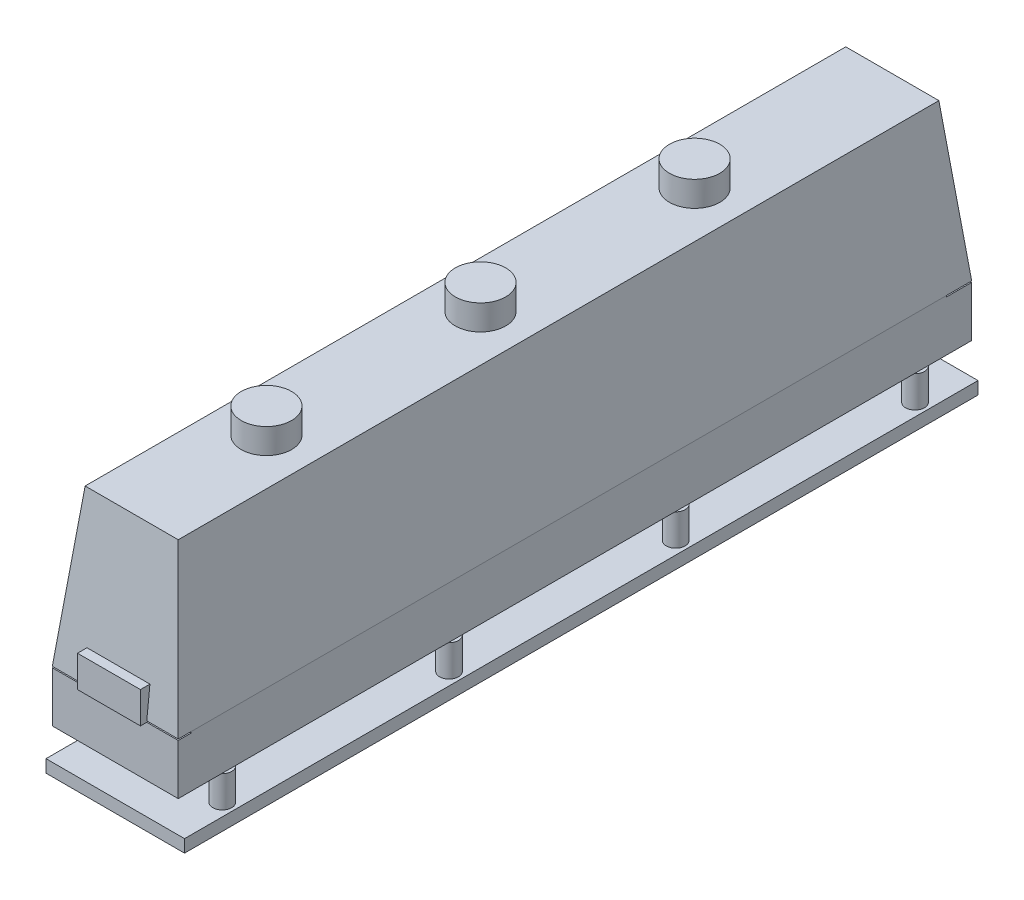
SolidWorks part; units mm, degrees
ref_plane "Front Plane" through (0, 0, 0) normal (0, 0, 1) x (1, 0, 0)
ref_plane "Top Plane" through (0, 0, 0) normal (0, 1, 0) x (1, 0, 0)
ref_plane "Right Plane" through (0, 0, 0) normal (1, 0, 0) x (0, 0, -1)
other "Configuration Table"
sketch "Sketch1" plane through (0, 0, 0) normal (0, 1, 0) x (1, 0, 0)
  line L1 (-550, 2600) -> (550, 2600)
  line L2 (-550, 2600) -> (-550, 8900)
  line L3 (-550, 8900) -> (550, 8900)
  line L4 (550, 2600) -> (550, 8900)
extrude "Boss-Extrude1" add sketch "Sketch1" along normal blind 100
sketch "Sketch2" plane through (0, 0, 0) normal (0, 1, 0) x (1, 0, 0)
  circle A0 centre (-450, 3000) radius 75
extrude "Boss-Extrude2" add sketch "Sketch2" along normal blind 250 from offset 100
sketch "Sketch3" plane through (0, 0, 0) normal (0, 1, 0) x (1, 0, 0)
  circle A0 centre (-450, 4800) radius 75
extrude "Boss-Extrude3" add sketch "Sketch3" along normal blind 250 from offset 100
sketch "Sketch4" plane through (0, 0, 0) normal (0, 1, 0) x (1, 0, 0)
  circle A0 centre (-450, 6600) radius 75
extrude "Boss-Extrude4" add sketch "Sketch4" along normal blind 250 from offset 100
sketch "Sketch5" plane through (0, 0, 0) normal (0, 1, 0) x (1, 0, 0)
  circle A0 centre (-450, 8500) radius 75
extrude "Boss-Extrude5" add sketch "Sketch5" along normal blind 250 from offset 100
sketch "Sketch6" plane through (0, 0, 0) normal (0, 1, 0) x (1, 0, 0)
  circle A0 centre (450, 3000) radius 75
extrude "Boss-Extrude6" add sketch "Sketch6" along normal blind 250 from offset 100
sketch "Sketch7" plane through (0, 0, 0) normal (0, 1, 0) x (1, 0, 0)
  circle A0 centre (450, 4800) radius 75
extrude "Boss-Extrude7" add sketch "Sketch7" along normal blind 250 from offset 100
sketch "Sketch8" plane through (0, 0, 0) normal (0, 1, 0) x (1, 0, 0)
  circle A0 centre (450, 6600) radius 75
extrude "Boss-Extrude8" add sketch "Sketch8" along normal blind 250 from offset 100
sketch "Sketch9" plane through (0, 0, 0) normal (0, 1, 0) x (1, 0, 0)
  circle A0 centre (450, 8500) radius 75
extrude "Boss-Extrude9" add sketch "Sketch9" along normal blind 250 from offset 100
sketch "Sketch10" plane through (0, 0, 0) normal (0, 1, 0) x (1, 0, 0)
  line L0 (-550, 2600) -> (550, 2600) construction
  line L1 (-500, 2600) -> (500, 2600)
  line L2 (-500, 2600) -> (-500, 8900)
  line L3 (-500, 8900) -> (500, 8900)
  line L4 (500, 2600) -> (500, 8900)
  line L5 (550, 8900) -> (-550, 8900) construction
extrude "Boss-Extrude10" add sketch "Sketch10" along normal blind 400 from offset 350
sketch "Sketch11" plane through (0, 0, 0) normal (0, 1, 0) x (1, 0, 0)
  line L1 (-250, 2550) -> (250, 2550)
  line L2 (-250, 2550) -> (-250, 2850)
  line L3 (-250, 2850) -> (250, 2850)
  line L4 (250, 2550) -> (250, 2850)
extrude "Boss-Extrude11" add sketch "Sketch11" along normal blind 250 from offset 750
sketch "Sketch12" plane through (0, 0, 0) normal (0, 1, 0) x (1, 0, 0)
  line L0 (500, 2600) -> (500, 8900) construction
  line L1 (-500, 2700) -> (500, 2700)
  line L2 (-500, 2700) -> (-500, 8700)
  line L3 (-500, 8700) -> (500, 8700)
  line L4 (500, 2700) -> (500, 8700)
extrude "Boss-Extrude12" add sketch "Sketch12" along normal blind 10 from offset 750
sketch "Sketch13" plane through (0, 0, 0) normal (0, 1, 0) x (1, 0, 0)
  line L0 (-550, 2600) -> (550, 2600) construction
  line L1 (-500, 2600) -> (500, 2600)
  line L2 (-500, 2600) -> (-500, 8900)
  line L3 (-500, 8900) -> (500, 8900)
  line L4 (500, 2600) -> (500, 8900)
extrude "Boss-Extrude13" add sketch "Sketch13" along normal blind 1240 draft 6 from offset 760
sketch "Sketch14" plane through (0, 0, 0) normal (0, 1, 0) x (1, 0, 0)
  circle A0 centre (0, 3800) radius 200
extrude "Boss-Extrude14" add sketch "Sketch14" along normal blind 200 from offset 2000
sketch "Sketch15" plane through (0, 0, 0) normal (0, 1, 0) x (1, 0, 0)
  circle A0 centre (0, 5500) radius 200
extrude "Boss-Extrude15" add sketch "Sketch15" along normal blind 200 from offset 2000
sketch "Sketch16" plane through (0, 0, 0) normal (0, 1, 0) x (1, 0, 0)
  circle A0 centre (0, 7200) radius 200
extrude "Boss-Extrude16" add sketch "Sketch16" along normal blind 200 from offset 2000
sketch "Sketch17" plane through (0, 0, 0) normal (0, 1, 0) x (1, 0, 0)
  line L1 (-250, 8700) -> (250, 8700)
  line L2 (-250, 8700) -> (-250, 8950)
  line L3 (-250, 8950) -> (250, 8950)
  line L4 (250, 8700) -> (250, 8950)
extrude "Boss-Extrude17" add sketch "Sketch17" along normal blind 150 from offset 600
